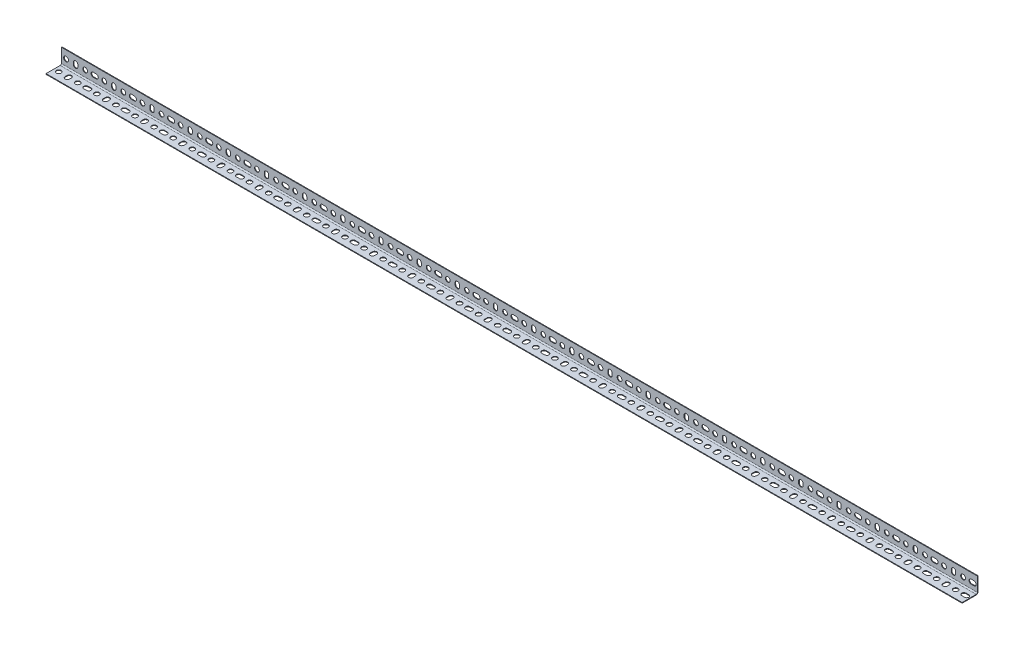
SolidWorks part; units mm, degrees
ref_plane "Front Plane" through (0, 0, 0) normal (0, 0, 1) x (1, 0, 0)
ref_plane "Top Plane" through (0, 0, 0) normal (0, 1, 0) x (1, 0, 0)
ref_plane "Right Plane" through (0, 0, 0) normal (1, 0, 0) x (0, 0, -1)
sketch "Sketch1" plane through (0, 0, 0) normal (1, 0, 0) x (0, 0, -1)
  line L0 (-31.75, 1.2192) -> (-1.2192, 1.2192)
  line L1 (0, 0) -> (-31.75, 0)
  line L2 (0, 0) -> (0, 31.75)
  line L3 (0, 31.75) -> (-1.2192, 31.75)
  line L4 (-31.75, 0) -> (-31.75, 1.2192)
  line L5 (-1.2192, 1.2192) -> (-1.2192, 31.75)
extrude "Boss-Extrude1" add sketch "Sketch1" along normal mid plane 1828.8
sketch "Sketch2" plane through (0, 0, 0) normal (0, 0, 1) x (1, 0, 0)
  line L0 (-904.875, 15.875) -> (-923.925, 15.875) construction
  line L2 (-904.875, 15.875) -> (-885.825, 15.875) construction
  line L3 (-914.4, 0) -> (-914.4, 31.75) construction
  line L4 (-885.825, 13.9065) -> (-885.825, 17.8435) construction
  line L5 (-890.1938, 13.9065) -> (-890.1938, 17.8435)
  line L6 (-881.4562, 13.9065) -> (-881.4562, 17.8435)
  line L7 (-885.825, 15.875) -> (-866.775, 15.875) construction
  line L8 (-866.775, 15.875) -> (-847.725, 15.875) construction
  line L9 (-850.4936, 15.875) -> (-844.9564, 15.875) construction
  line L10 (-850.4936, 20.2438) -> (-844.9564, 20.2438)
  line L11 (-850.4936, 11.5062) -> (-844.9564, 11.5062)
  circle A0 centre (-904.875, 15.875) radius 4.7879
  arc A1 (-890.1938, 13.9065) -> (-881.4562, 13.9065) centre (-885.825, 13.9065) ccw
  arc A2 (-881.4562, 17.8435) -> (-890.1938, 17.8435) centre (-885.825, 17.8435) ccw
  circle A3 centre (-866.775, 15.875) radius 4.7879
  arc A4 (-850.4936, 20.2438) -> (-850.4936, 11.5062) centre (-850.4936, 15.875) ccw
  arc A5 (-844.9564, 11.5062) -> (-844.9564, 20.2438) centre (-844.9564, 15.875) ccw
  point P2 (-914.4, 15.875)
  point P9 (-885.825, 15.875)
  point P19 (-847.725, 15.875)
  dimension "D1" = 8.7376
  dimension "D3" = 14.2748
  dimension "D4" = 8.7376
  dimension "D2" = 12.6746
extrude "Cut-Extrude1" cut sketch "Sketch2" along normal through all
pattern_linear "LPattern1" count 24 spacing 76.2 along (1, 0, 0) of "Cut-Extrude1"
ref_plane "Plane1" through (0, 0, 0) normal (0, -0.7071, 0.7071) x (1, 0, 0)
mirror "Mirror1" about plane through (0, 0, 0) normal (0, -0.7071, 0.7071) of "LPattern1"
fillet "Fillet1" radius 2.4384 1 edges at (0, 1.2192, 1.2192)
fillet "Fillet2" radius 3.6576 1 edges at (0, 0, 0)
sketch "Sketch3" plane through (0, 0, 0) normal (0, 0, 1) x (1, 0, 0)
  line L0 (-914.4, 31.75) -> (-800.1, 31.75) construction
  line L1 (914.4, 31.75) -> (-914.4, 31.75) construction
  line L2 (-800.1, 31.75) -> (-800.1, 1.2192) construction
  line L3 (914.4, 1.2192) -> (-914.4, 1.2192) construction
  line L4 (914.4, 31.75) -> (800.1, 31.75) construction
  line L5 (800.1, 31.75) -> (800.1, 0) construction
  line L6 (914.4, 0) -> (-914.4, 0) construction
  dimension "D1" = 114.3
equation "\"D3@LPattern1\" = \"Hole Center@Sketch2\" * 4"
equation "\"D1@LPattern1\" = \"Length@Boss-Extrude1\" / \"D3@LPattern1\""
equation "\"D1@Fillet1\"=\"Wall Thick.@Sketch1\"*2"
equation "\"D1@Fillet2\"=\"Wall Thick.@Sketch1\"*3"
